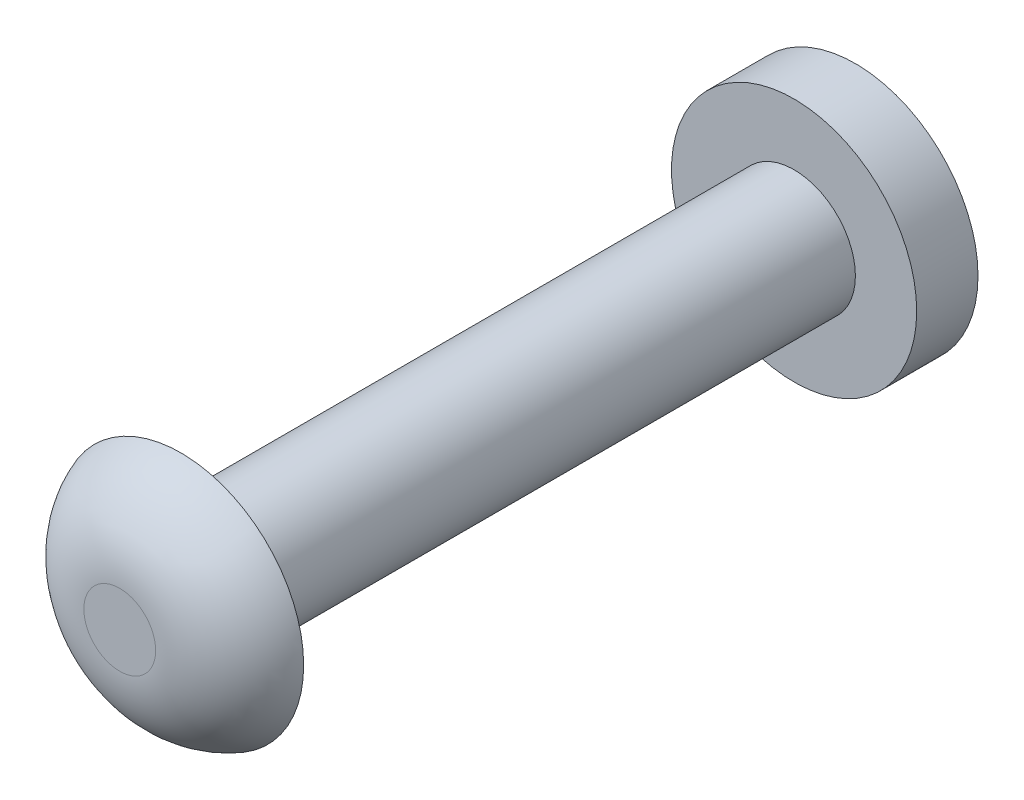
SolidWorks part; units mm, degrees
ref_plane "Front Plane" through (0, 0, 0) normal (0, 0, 1) x (1, 0, 0)
ref_plane "Top Plane" through (0, 0, 0) normal (0, 1, 0) x (1, 0, 0)
ref_plane "Right Plane" through (0, 0, 0) normal (1, 0, 0) x (0, 0, -1)
sketch "Sketch1" plane through (0, 0, 0) normal (0, 0, 1) x (1, 0, 0)
  circle A0 centre (0, 0) radius 5
  dimension "D1" = 10
extrude "Boss-Extrude1" add sketch "Sketch1" along normal mid plane 50
sketch "Sketch2" plane through (0, 0, 25) normal (0, 0, 1) x (1, 0, 0)
  circle A0 centre (0, 0) radius 10
  dimension "D1" = 20
extrude "Boss-Extrude2" add sketch "Sketch2" along normal blind 5
mirror "Mirror1" about plane through (0, 0, 0) normal (0, 0, 1) of "Boss-Extrude2"
fillet "Fillet1" radius 7.5 1 edges at (10, 0, 30)
